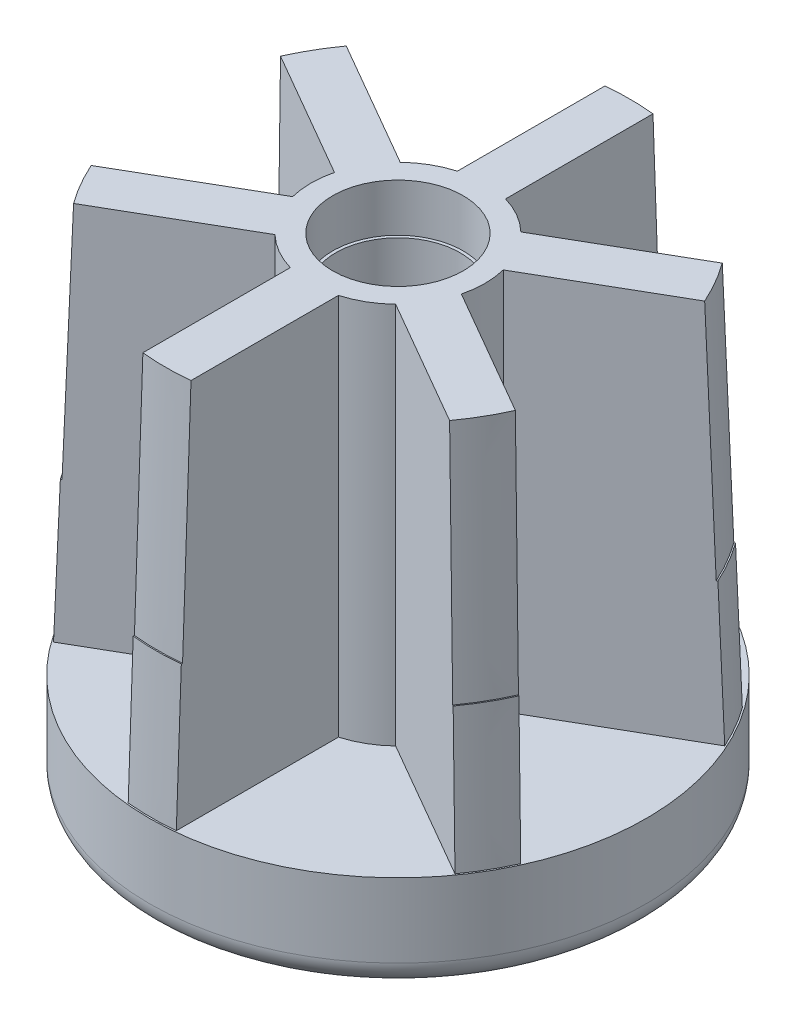
SolidWorks part; units mm, degrees
ref_plane "Front Plane" through (0, 0, 0) normal (0, 0, 1) x (1, 0, 0)
ref_plane "Top Plane" through (0, 0, 0) normal (0, 1, 0) x (1, 0, 0)
ref_plane "Right Plane" through (0, 0, 0) normal (1, 0, 0) x (0, 0, -1)
sketch "Sketch1" plane through (0, 0, 0) normal (1, 0, 0) x (0, 0, -1)
  line L0 (0, 24.6063) -> (0, -24.6063) construction
  line L1 (0, -24.6063) -> (25.4, -24.6063)
  line L2 (25.4, -24.6063) -> (25.4, -14.5097)
  line L3 (25.4, -14.5097) -> (0, -14.5097)
  line L4 (6.35, -24.6063) -> (6.35, -5.5563)
  line L5 (6.35, -5.5563) -> (0, -5.5563)
  line L6 (7.62, -24.6063) -> (7.62, -5.5563)
  line L7 (7.62, -5.5563) -> (6.35, -5.5563)
  line L8 (8.89, -14.5097) -> (8.89, 24.6062)
  line L9 (8.89, 24.6062) -> (0, 24.6063)
  line L10 (24.6063, -14.5097) -> (24.6063, 24.6063)
  line L11 (24.6063, 24.6063) -> (8.89, 24.6062)
  line L12 (24.6063, -14.5097) -> (23.9235, 24.6063)
  line L13 (7.62, -5.5563) -> (8.89, -5.5563) construction
  line L14 (6.5615, -24.4841) -> (4.8694, -25.4611) construction
  line L15 (4.8694, -25.4611) -> (6.5615, -26.438) construction
  line L16 (6.5615, -26.438) -> (6.5615, -24.4841) construction
  line L17 (6.4558, -24.5452) -> (6.4558, -26.3769)
  line L18 (6.4558, -26.3769) -> (5.0809, -25.5832)
  line L19 (5.0809, -25.5832) -> (5.0809, -25.3389)
  line L20 (5.0809, -25.3389) -> (6.4558, -24.5452)
  line L21 (5.0809, -25.4611) -> (4.8694, -25.4611) construction
  line L22 (6.35, -24.6063) -> (6.35, -26.3159) construction
  line L23 (6.5615, -25.4611) -> (6.35, -25.4611) construction
  line L24 (-6.35, -24.6063) -> (-6.35, -5.5563)
  point P2 (0, 0)
  point P16 (8.255, -5.5563)
  point P31 (6.4558, -25.4611)
  point P33 (24.6063, -14.5097)
  point P35 (-6.35, -15.0813)
  point P36 (6.35, -24.6063)
  point P37 (6.35, -15.0813)
  dimension "Base Diameter" = 50.8
  dimension "Thread Diameter" = 12.7
  dimension "Thread Depth" = 19.05
  dimension "D1" = 15.24
  dimension "D4" = 17.78
  dimension "Insert Depth" = 39.116
  dimension "Overall Height" = 49.2125
  dimension "For Leg ID" = 49.2125
  dimension "D2" = 1
  dimension "Pitch" = 1.9538
  dimension "D5" = 0.2442
sketch "Sketch2" plane through (0, 0, 0) normal (0, 1, 0) x (1, 0, 0)
  line L0 (-2.4606, 24.4829) -> (2.4606, 24.4829)
  line L1 (-2.4606, 24.4829) -> (-2.4606, 8.5427)
  line L2 (-2.4606, 8.5427) -> (2.4606, 8.5427)
  line L3 (2.4606, 8.5427) -> (2.4606, 24.4829)
  circle A0 centre (0, 0) radius 24.6063
  circle A1 centre (0, 0) radius 8.89
  dimension "D1" = 4.9213
sketch "Sketch8" plane through (0, 0, 0) normal (1, 0, 0) x (0, 0, -1)
  line L0 (8.89, -14.5097) -> (8.89, 24.6062)
  line L1 (8.89, 24.6062) -> (6.35, 24.6062)
  line L2 (8.89, 24.6062) -> (0, 24.6062) construction
  line L3 (6.35, 24.6062) -> (6.35, -5.5563)
  line L4 (6.35, -5.5563) -> (7.62, -5.5563)
  line L9 (0, 24.6063) -> (0, -14.5097) construction
  line L10 (7.62, -5.5563) -> (7.62, -24.6063)
  line L11 (7.62, -24.6063) -> (25.4, -24.6063)
  line L12 (25.4, -24.6063) -> (25.4, -14.5097)
  line L13 (25.4, -14.5097) -> (8.89, -14.5097)
revolve "Revolve2" add sketch "Sketch8" angle 360 about L9
sketch "Sketch9" plane through (-13.335, -14.5097, 0) normal (0, 1, 0) x (0, 0, -1)
  line L4 (8.5427, -10.8744) -> (8.5427, -15.7956)
  line L7 (8.5427, -10.8744) -> (25.2805, -10.8744)
  line L8 (8.5427, -15.7956) -> (25.2805, -15.7956)
  circle A0 centre (0, -13.335) radius 25.4 construction
  arc A1 (25.2805, -15.7956) -> (25.2805, -10.8744) centre (0, -13.335) ccw
extrude "Boss-Extrude3" add sketch "Sketch9" along normal up to vertex (39.116 mm away) up to point (0, 24.6063, 0)
pattern_circular "CirPattern2" count 6 over 360 about axis through (0, -24.6063, 0) along (0, 1, 0) of "Boss-Extrude3"
sketch "Sketch15" plane through (0, 0, 0) normal (1, 0, 0) x (0, 0, -1)
  line L0 (24.6063, -14.5097) -> (25.4, -14.5097) construction
  line L1 (25.24, -14.5097) -> (24.7333, 0)
  line L2 (24.7333, 0) -> (24.6063, 0)
  line L3 (6.35, 24.6062) -> (-6.35, 24.6062) construction
  line L4 (24.6063, 0) -> (23.747, 24.6062)
  line L5 (23.747, 24.6062) -> (25.4, 24.6063)
  line L6 (25.4, 24.6063) -> (25.4, -14.5097)
  line L7 (25.4, -14.5097) -> (25.24, -14.5097)
  line L8 (6.35, 24.6062) -> (6.6675, 24.6062)
  line L9 (6.35, 24.6062) -> (6.35, 19.7167)
  line L10 (6.35, 19.7167) -> (6.6675, 19.7167)
  line L11 (6.6675, 24.6062) -> (6.6675, 19.7167)
  dimension "D1" = 2
  dimension "D2" = 0.127
  dimension "D3" = 0.3175
  dimension "D4" = 4.8895
revolve "Cut-Revolve1" cut sketch "Sketch15" angle 360 about L0
sketch "Sketch10" plane through (0, 0, 0) normal (1, 0, 0) x (0, 0, -1)
  line L0 (0, -5.5563) -> (0, -24.6063) construction
  line L2 (7.62, -5.5563) -> (6.35, -5.5563)
  line L3 (7.62, -5.5563) -> (7.62, -24.6063)
  line L4 (7.62, -24.6063) -> (6.35, -24.6063)
  line L5 (6.35, -5.5563) -> (6.35, -24.6063)
revolve "Revolve3" add sketch "Sketch10" angle 360 about L0
sketch "Sketch11" plane through (0, -24.6063, 0) normal (0, -1, 0) x (1, 0, 0)
  circle A0 centre (0, 0) radius 6.35 construction
  circle A1 centre (0, 0) radius 6.35
fillet "Fillet2" radius 2.54 1 edges at (0, -24.6063, 25.4)
curve "Helix/Spiral1" pitch 1.9538 height 21.0038 radius 6.35 centre (0, -24.6063, 0) axis (0, 1, 0) start towards (0, 0, -1)
sketch "Sketch12" plane through (0, 0, 0) normal (1, 0, 0) x (0, 0, -1)
  line L0 (6.4558, -24.5452) -> (6.4558, -26.3769) construction
  line L1 (5.0809, -25.3389) -> (6.4558, -24.5452) construction
  line L2 (5.0809, -25.5832) -> (5.0809, -25.3389) construction
  line L3 (6.4558, -26.3769) -> (5.0809, -25.5832) construction
  line L4 (6.4558, -24.5452) -> (6.4558, -26.3769)
  line L5 (5.0809, -25.3389) -> (6.4558, -24.5452)
  line L6 (5.0809, -25.5832) -> (5.0809, -25.3389)
  line L7 (6.4558, -26.3769) -> (5.0809, -25.5832)
sweep "Sweep1" add profiles "Sketch12" path "Helix/Spiral1"
sketch "Sketch13" plane through (0, -24.6063, 0) normal (0, -1, 0) x (1, 0, 0)
  circle A0 centre (0, 0) radius 6.5615
extrude "Cut-Extrude1" cut sketch "Sketch13" against normal up to vertex (19.05 mm away) draft 45 and the other way through all up to point (0, -5.5563, 0)
sketch "Sketch14" plane through (0, -5.5563, 0) normal (0, 1, 0) x (1, 0, 0)
  circle A1 centre (0, 0) radius 6.5615
  circle A2 centre (0, 0) radius 6.5615
  dimension "D1" = 0
extrude "Cut-Extrude2" cut sketch "Sketch14" against normal up to vertex (19.05 mm away) draft 45 and the other way through all up to point (0, -24.6063, 0)
equation "\"D1@Sketch1\"=\"Thread Diameter@Sketch1\"*1.2"
equation "\"D1@Sketch2\" = \"For Leg ID@Sketch1\" * 0.1"
equation "\"D4@Sketch1\"=\"Thread Diameter@Sketch1\"*1.4"
equation "\"D5@Sketch1\" = \"Pitch@Sketch1\" / 8"
equation "\"D4@Helix/Spiral1\"=\"Pitch@Sketch1\""
equation "\"D3@Helix/Spiral1\"=\"Pitch@Sketch1\"+\"Thread Depth@Sketch1\""
equation "\"D1@Fillet2\"=0.05*\"Base Diameter@Sketch1\""
equation "\"D4@Sketch15\"=\"Insert Depth@Sketch1\"/8"
